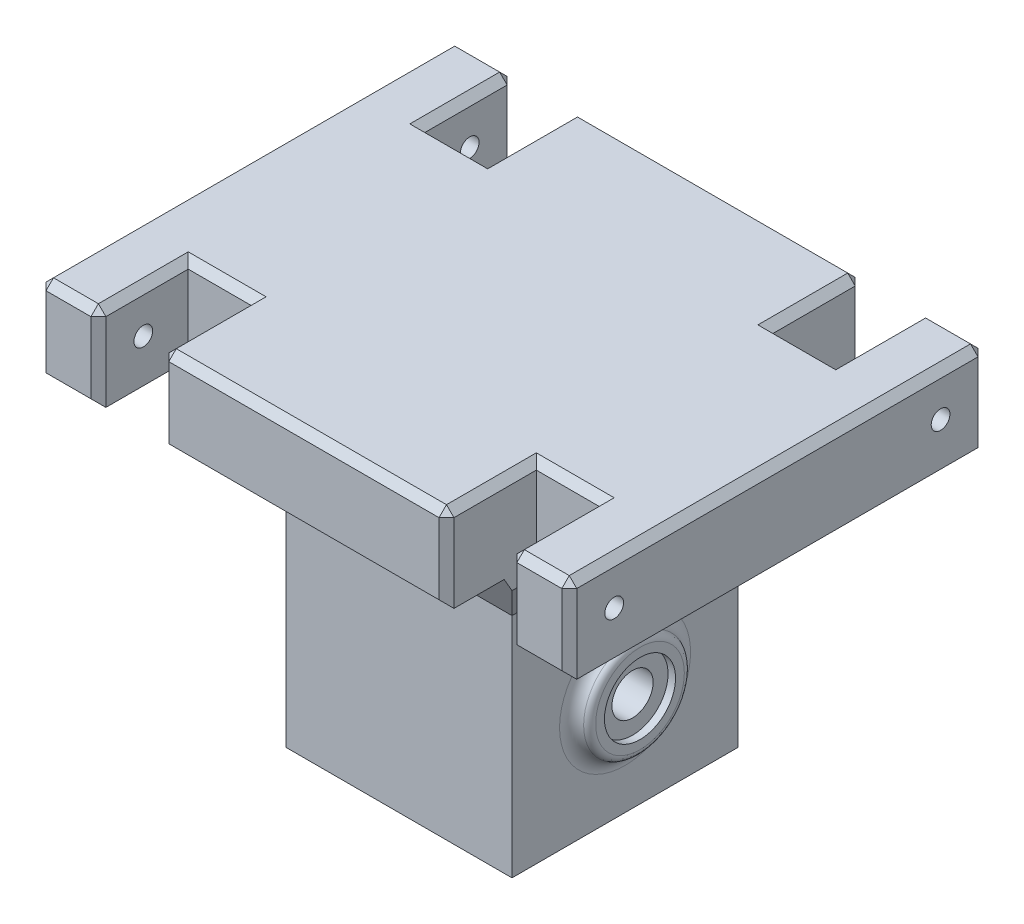
SolidWorks part; units mm, degrees
ref_plane "Front Plane" through (0, 0, 0) normal (0, 0, 1) x (1, 0, 0)
ref_plane "Top Plane" through (0, 0, 0) normal (0, 1, 0) x (1, 0, 0)
ref_plane "Right Plane" through (0, 0, 0) normal (1, 0, 0) x (0, 0, -1)
sketch "Sketch1" plane through (0, 0, 0) normal (0, 1, 0) x (1, 0, 0)
  line L0 (-23.25, 0) -> (23.25, 0) construction
  line L1 (23.25, 15.8) -> (23.25, -15.8) construction
  line L2 (19.05, 15.8) -> (27.45, 15.8)
  line L3 (19.05, 15.8) -> (19.05, 27.8)
  line L4 (19.05, 27.8) -> (27.45, 27.8)
  line L5 (27.45, 27.8) -> (27.45, 15.8)
  line L6 (19.05, -15.8) -> (27.45, -15.8)
  line L7 (27.45, -27.8) -> (27.45, -15.8)
  line L8 (19.05, -27.8) -> (27.45, -27.8)
  line L9 (19.05, -15.8) -> (19.05, -27.8)
  line L10 (0, 0) -> (0, 17.3954) construction
  line L11 (-19.05, -15.8) -> (-27.45, -15.8)
  line L12 (-23.25, 15.8) -> (-23.25, -15.8) construction
  line L13 (-19.05, -15.8) -> (-19.05, -27.8)
  line L14 (-19.05, -27.8) -> (-27.45, -27.8)
  line L15 (-27.45, -27.8) -> (-27.45, -15.8)
  line L16 (-27.45, 27.8) -> (-27.45, 15.8)
  line L17 (-19.05, 27.8) -> (-27.45, 27.8)
  line L18 (-19.05, 15.8) -> (-19.05, 27.8)
  line L19 (-19.05, 15.8) -> (-27.45, 15.8)
  line L21 (-35.45, -27.8) -> (35.45, -27.8)
  line L22 (-35.45, -27.8) -> (-35.45, 27.8)
  line L23 (-35.45, 27.8) -> (35.45, 27.8)
  line L24 (35.45, -27.8) -> (35.45, 27.8)
  line L25 (-35.45, -27.8) -> (35.45, 27.8) construction
  line L26 (-35.45, 27.8) -> (35.45, -27.8) construction
  dimension "D1" = 23.25
  dimension "D2" = 31.6
  dimension "D3" = 8.4
  dimension "D4" = 12
  dimension "D5" = 8
extrude "Boss-Extrude1" add sketch "Sketch1" along normal blind 11.5 contours L21 L24 L23 L5 L2 L3 L18 L19 L16 L22 L15 L11 L13 L9 L6 L7 region at (0, 0, 0)
sketch "Sketch2" plane through (0, 0, 0) normal (0, -1, 0) x (1, 0, 0)
  line L1 (-10.1, -10.1) -> (10.1, -10.1)
  line L2 (-10.1, -10.1) -> (-10.1, 10.1)
  line L3 (-10.1, 10.1) -> (10.1, 10.1)
  line L4 (10.1, -10.1) -> (10.1, 10.1)
  line L5 (-10.1, -10.1) -> (10.1, 10.1) construction
  line L6 (-10.1, 10.1) -> (10.1, -10.1) construction
  line L7 (-15.1, -15.1) -> (15.1, -15.1)
  line L8 (-15.1, -15.1) -> (-15.1, 15.1)
  line L9 (-15.1, 15.1) -> (15.1, 15.1)
  line L10 (15.1, -15.1) -> (15.1, 15.1)
  line L11 (-15.1, -15.1) -> (15.1, 15.1) construction
  line L12 (-15.1, 15.1) -> (15.1, -15.1) construction
  point P0 (0, 0)
  point P6 (0, 0)
  dimension "D1" = 20.2
  dimension "D2" = 20.2
  dimension "D3" = 5
  dimension "D4" = 5
extrude "Boss-Extrude2" add sketch "Sketch2" along normal blind 40
sketch "s" plane through (-15.1, 0, 0) normal (-1, 0, 0) x (0, 0, 1)
  line L0 (0, -40) -> (0, -24.8) construction
  line L1 (15.1, -40) -> (-15.1, -40) construction
  circle A0 centre (0, -24.8) radius 2.75
  circle A1 centre (0, -24.8) radius 4.75
  circle A2 centre (0, -24.8) radius 6.75
  dimension "D1" = 5.5
  dimension "D2" = 9.5
  dimension "D3" = 13.5
  dimension "D4" = 15.2
extrude "Cut-Extrude1" cut sketch "s" against normal blind 50 contours A0 region at (-15.1, -24.8, 0)
extrude "Boss-Extrude3" add sketch "s<3>" along normal blind 1 contours A1 A0 region at (-15.1, -24.8, -4.6156)
sketch "s<3>" plane through (-15.1, 0, 0) normal (-1, 0, 0) x (0, 0, 1) same geometry as "s"
extrude "Boss-Extrude4" add sketch "s<4>" along normal blind 2 contours A2 A1 region at (-15.1, -24.8, -6.5591)
sketch "s<4>" plane through (-15.1, 0, 0) normal (-1, 0, 0) x (0, 0, 1) same geometry as "s"
mirror "Mirror3" about plane through (0, 0, 0) normal (1, 0, 0) of "Boss-Extrude4", "Boss-Extrude3"
fillet "Fillet1" radius 2 2 edges at (-15.1, -24.8, -6.75) (15.1, -24.8, 6.75)
fillet "Fillet2" radius 1 2 edges at (-17.1, -24.8, 6.75) (17.1, -24.8, 6.75)
chamfer "Chamfer1" distance 5 angle 60 4 edges at (-15.1, 0, 0) (0, 0, 15.1) (15.1, 0, 0) (0, 0, -15.1) first distance on face at (0, 0, 0)
ref_plane "Plane1" through (0, 0, 0) normal (0, -1, 0) x (-1, 0, 0)
sketch "Sketch3" plane through (35.45, 0, 0) normal (1, 0, 0) x (0, 0, -1)
  line L0 (-15.8, 11.5) -> (-27.8, 0) construction
  line L1 (-27.8, 11.5) -> (27.8, 11.5) construction
  line L2 (0, 0) -> (0, 5.8632) construction
  line L3 (-27.8, 0) -> (27.8, 0) construction
  circle A0 centre (-21.8, 5.75) radius 1.25
  circle A1 centre (21.8, 5.75) radius 1.25
  dimension "D1" = 2.5
extrude "Cut-Extrude2" cut sketch "Sketch3" against normal blind 10
mirror "Mirror4" about plane through (0, 0, 0) normal (1, 0, 0) of "Cut-Extrude2"
chamfer "Chamfer2" distance 1 angle 45 46 edges at (0, -40, 10.1) (-10.1, -40, 0) (0, -40, -10.1) (10.1, -40, 0) (0, -40, -15.1) (-15.1, -40, 0) (0, -40, 15.1) (15.1, -40, 0) (-27.45, 5.75, -27.8) (-31.45, 0, -27.8) (-35.45, 5.75, -27.8) (27.45, 11.5, 21.8) (23.25, 11.5, 15.8) (19.05, 11.5, 21.8) (-19.05, 5.75, 27.8) (0, 0, 27.8) (19.05, 5.75, 27.8) (0, 11.5, 27.8) (-19.05, 11.5, 21.8) (-23.25, 11.5, 15.8) (-27.45, 11.5, 21.8) (27.45, 5.75, 27.8) (31.45, 11.5, 27.8) (31.45, 0, 27.8) (35.45, 5.75, 27.8) (35.45, 11.5, 0) (35.45, 5.75, -27.8) (31.45, 11.5, -27.8) (31.45, 0, -27.8) (27.45, 5.75, -27.8) (27.45, 11.5, -21.8) (23.25, 11.5, -15.8) (19.05, 11.5, -21.8) (19.05, 5.75, -27.8) (0, 11.5, -27.8) (0, 0, -27.8) (-19.05, 5.75, -27.8) (-19.05, 11.5, -21.8) (-23.25, 11.5, -15.8) (-27.45, 11.5, -21.8) (-31.45, 11.5, -27.8) (-35.45, 11.5, 0) (-35.45, 5.75, 27.8) (-31.45, 11.5, 27.8) (-27.45, 5.75, 27.8) (-31.45, 0, 27.8)
